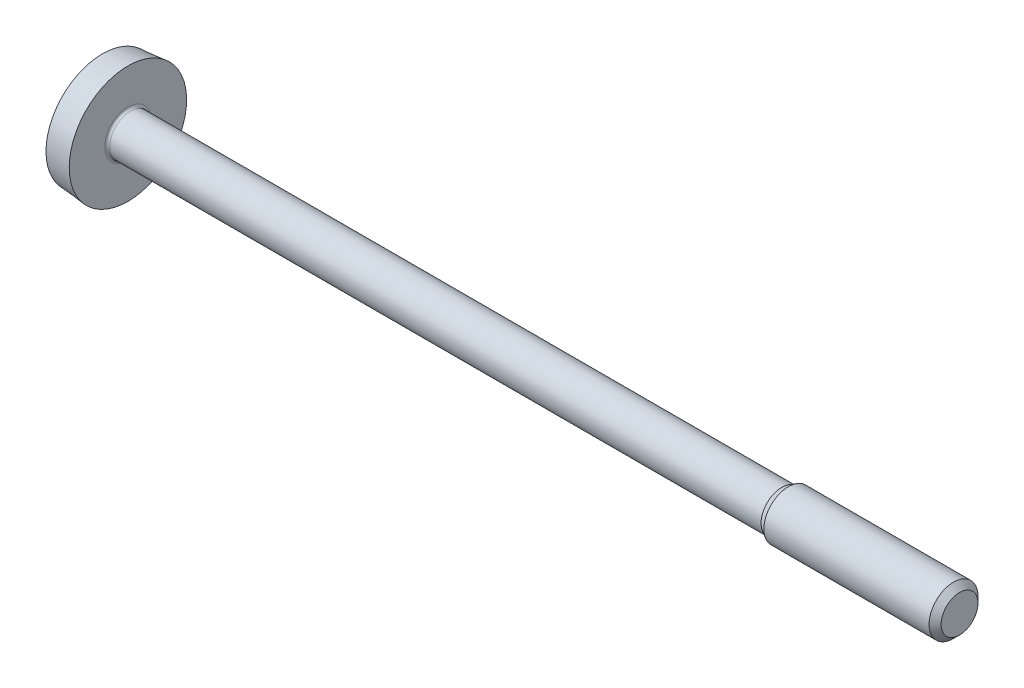
SolidWorks part; units mm, degrees
ref_plane "Ebene vorne" through (0, 0, 0) normal (0, 0, 1) x (1, 0, 0)
ref_plane "Ebene oben" through (0, 0, 0) normal (0, 1, 0) x (1, 0, 0)
ref_plane "Ebene rechts" through (0, 0, 0) normal (1, 0, 0) x (0, 0, -1)
sketch "Skizze1" plane through (0, 0, 0) normal (0, 0, 1) x (1, 0, 0)
  line L0 (-1.04, 2.309) -> (0, 2.4)
  line L1 (0, 2.4) -> (0, 0.945)
  line L2 (0.1, 0.845) -> (26.7315, 0.845)
  line L3 (26.7315, 0.845) -> (27, 1)
  line L4 (27, 1) -> (33.7545, 1)
  line L5 (33.7545, 1) -> (34, 0.7545)
  line L6 (34, 0.7545) -> (34, 0)
  line L7 (34, 0) -> (-1.6, 0)
  line L8 (34, 0) -> (-1.6, 0) construction
  arc A0 (-1.6, 0) -> (-1.04, 2.309) centre (3.4403, 0) cw
  arc A1 (0, 0.945) -> (0.1, 0.845) centre (0.1, 0.945) ccw
revolve "Rotation1" add sketch "Skizze1" angle 360 about L8 reverse direction yes
cosmetic thread "Gewindedarstellung1" parameters "D1"=7, "D2"=1.509
ref_plane "Ebene1" through (-1.04, 0, 0) normal (1, 0, 0) x (0, 0, -1)
sketch "Skizze2" plane through (-1.04, 0, 0) normal (1, 0, 0) x (0, 0, -1)
  line L0 (-1, 0.29) -> (-1, -0.29)
  line L1 (-1, -0.29) -> (-0.29, -0.29)
  line L2 (-0.29, -0.29) -> (-0.29, -2.5)
  line L3 (-0.29, -2.5) -> (0.29, -2.5)
  line L4 (0.29, -2.5) -> (0.29, -0.29)
  line L5 (0.29, -0.29) -> (1, -0.29)
  line L6 (1, -0.29) -> (1, 0.29)
  line L7 (1, 0.29) -> (0.29, 0.29)
  line L8 (0.29, 0.29) -> (0.29, 2.5)
  line L9 (0.29, 2.5) -> (-0.29, 2.5)
  line L10 (-0.29, 2.5) -> (-0.29, 0.29)
  line L11 (-0.29, 0.29) -> (-1, 0.29)
extrude "Schnitt-Linear austragen1" cut sketch "Skizze2" against normal blind 0.6
ref_plane "ANBAU XY" through (0, 0, 0) normal (1, 0, 0) x (0, 0, -1)
ref_plane "ANBAU XZ" through (0, 0, 0) normal (0, -1, 0) x (-1, 0, 0)
ref_plane "ANBAU YZ" through (0, 0, 0) normal (0, 0, -1) x (-1, 0, 0)
ref_axis "ANBAU X" through (0, 0, 80.9) along (0, 0, -1)
ref_axis "ANBAU Y" through (0, -50, 0) along (0, 1, 0)
ref_axis "ANBAU Z" through (80.9, 0, 0) along (-1, 0, 0)
sketch3d "ANBAU"
  point P0 (0, 0, 0)
